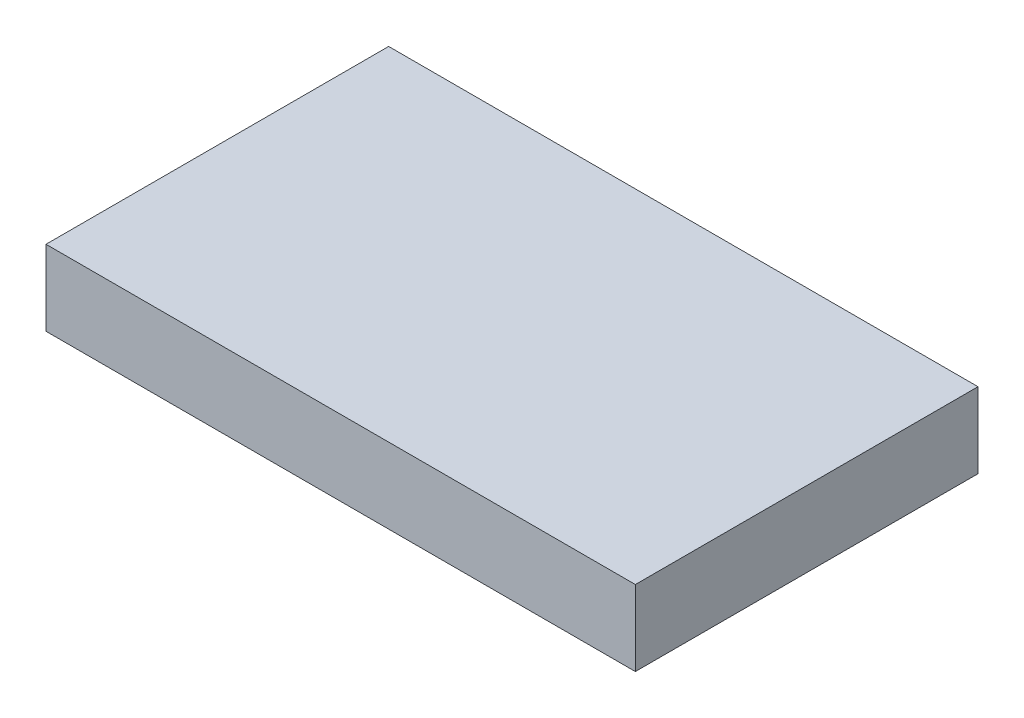
SolidWorks part; units mm, degrees
ref_plane "Front Plane" through (0, 0, 0) normal (0, 0, 1) x (1, 0, 0)
ref_plane "Top Plane" through (0, 0, 0) normal (0, 1, 0) x (1, 0, 0)
ref_plane "Right Plane" through (0, 0, 0) normal (1, 0, 0) x (0, 0, -1)
sketch "Sketch2" plane through (0, 0, 0) normal (0, 1, 0) x (1, 0, 0)
  line L1 (-21.844, -12.7) -> (21.844, -12.7)
  line L2 (-21.844, -12.7) -> (-21.844, 12.7)
  line L3 (-21.844, 12.7) -> (21.844, 12.7)
  line L4 (21.844, -12.7) -> (21.844, 12.7)
  line L5 (-21.844, -12.7) -> (21.844, 12.7) construction
  line L6 (-21.844, 12.7) -> (21.844, -12.7) construction
  point P0 (0, 0)
  dimension "D1" = 25.4
  dimension "D2" = 43.688
extrude "Boss-Extrude1" add sketch "Sketch2" along normal blind 5.588
